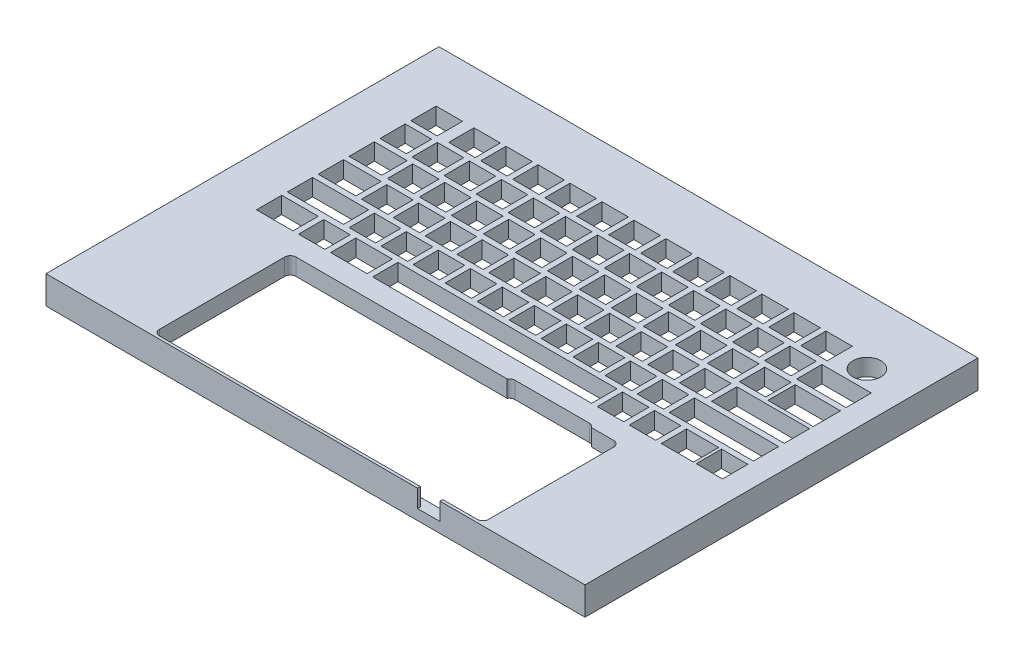
SolidWorks part; units mm, degrees
ref_plane "Front Plane" through (0, 0, 0) normal (0, 0, 1) x (1, 0, 0)
ref_plane "Top Plane" through (0, 0, 0) normal (0, 1, 0) x (1, 0, 0)
ref_plane "Right Plane" through (0, 0, 0) normal (1, 0, 0) x (0, 0, -1)
sketch "Sketch1" plane through (0, 0, 0) normal (0, 1, 0) x (1, 0, 0)
  line L0 (5.08, 5.08) -> (238.76, 5.08)
  line L1 (0, 0) -> (243.84, 0)
  line L2 (0, 0) -> (0, 177.8)
  line L3 (0, 177.8) -> (243.84, 177.8)
  line L4 (243.84, 0) -> (243.84, 177.8)
  line L5 (238.76, 5.08) -> (238.76, 172.72)
  line L6 (5.08, 172.72) -> (238.76, 172.72)
  line L7 (5.08, 5.08) -> (5.08, 172.72)
  dimension "D1" = 177.8
  dimension "D2" = 243.84
  dimension "D3" = 5.08
extrude "Boss-Extrude7" add sketch "Sketch1" along normal blind 12.7
sketch "Sketch6" plane through (0, 12.7, 0) normal (0, 1, 0) x (1, 0, 0)
  line L0 (5.08, 172.72) -> (5.08, 5.08)
  line L1 (5.08, 5.08) -> (238.76, 5.08)
  line L2 (238.76, 5.08) -> (238.76, 172.72)
  line L3 (238.76, 172.72) -> (5.08, 172.72)
extrude "Boss-Extrude8" add sketch "Sketch6" against normal blind 7.62
sketch "Sketch7" plane through (0, 12.7, 0) normal (0, 1, 0) x (1, 0, 0)
  line L0 (0, 0) -> (243.84, 0) construction
  line L1 (0, 177.8) -> (0, 0) construction
  line L2 (243.84, 0) -> (243.84, 177.8) construction
  line L3 (196.37, 1.27) -> (178.2581, 1.27)
  line L4 (47.47, 1.27) -> (47.47, 63.07)
  line L6 (196.37, 63.07) -> (196.37, 1.27)
  line L8 (47.47, 32.17) -> (0, 32.17) construction
  line L9 (196.37, 32.17) -> (243.84, 32.17) construction
  line L11 (168.0981, 0) -> (178.2581, 0)
  line L12 (178.2581, 0) -> (178.2581, 1.27)
  line L14 (157.9954, 1.27) -> (47.47, 1.27)
  line L15 (157.9954, 1.27) -> (168.0981, 1.27)
  line L16 (168.0981, 1.27) -> (168.0981, 0)
  line L18 (183.67, 64.34) -> (145.57, 64.34)
  line L20 (196.37, 63.07) -> (183.67, 63.07)
  line L21 (145.57, 63.07) -> (47.47, 63.07)
  line L22 (183.67, 63.07) -> (183.67, 64.34)
  line L23 (145.57, 63.07) -> (145.57, 64.34)
  dimension "D1" = 1.27
  dimension "D2" = 148.9
  dimension "D3" = 61.8
  dimension "D4" = 10.16
  dimension "D5" = 38.1
  dimension "D6" = 12.7
  dimension "D7" = 1.27
extrude "Cut-Extrude2" cut sketch "Sketch7" against normal blind 8 contours L4 L21 L23 L18 L22 L20 L6 L3 L12 L11 L16 L15 L14
fillet "Fillet1" radius 2.54 4 edges at (47.47, 8.89, -63.07) (47.47, 8.7, -1.27) (196.37, 8.7, -1.27) (196.37, 8.89, -63.07)
fillet "Fillet2" radius 2.54 2 edges at (145.57, 8.89, -64.34) (183.67, 8.89, -64.34)
sketch "Sketch8" plane through (0, 12.7, 0) normal (0, 1, 0) x (1, 0, 0)
  line L0 (50.5293, 86.591) -> (50.5293, 97.9956)
  line L1 (50.5293, 97.9956) -> (62.5181, 97.9956)
  line L2 (62.5181, 97.9956) -> (62.5181, 86.591)
  line L3 (62.5181, 86.591) -> (50.5293, 86.591)
  line L4 (76.9961, 86.591) -> (65.0073, 86.591)
  line L5 (65.0073, 86.591) -> (65.0073, 97.9956)
  line L6 (65.0073, 97.9956) -> (76.9961, 97.9956)
  line L7 (76.9961, 97.9956) -> (76.9961, 86.591)
  line L8 (91.4741, 86.591) -> (79.4853, 86.591)
  line L9 (79.4853, 86.591) -> (79.4853, 97.9956)
  line L10 (79.4853, 97.9956) -> (91.4741, 97.9956)
  line L11 (91.4741, 97.9956) -> (91.4741, 86.591)
  line L12 (105.9521, 86.591) -> (93.9633, 86.591)
  line L13 (93.9633, 86.591) -> (93.9633, 97.9956)
  line L14 (93.9633, 97.9956) -> (105.9521, 97.9956)
  line L15 (105.9521, 97.9956) -> (105.9521, 86.591)
  line L16 (120.4301, 86.591) -> (108.4413, 86.591)
  line L17 (108.4413, 86.591) -> (108.4413, 97.9956)
  line L18 (108.4413, 97.9956) -> (120.4301, 97.9956)
  line L19 (120.4301, 97.9956) -> (120.4301, 86.591)
  line L20 (134.9081, 86.591) -> (122.9193, 86.591)
  line L21 (122.9193, 86.591) -> (122.9193, 97.9956)
  line L22 (122.9193, 97.9956) -> (134.9081, 97.9956)
  line L23 (134.9081, 97.9956) -> (134.9081, 86.591)
  line L24 (149.3861, 86.591) -> (137.3973, 86.591)
  line L25 (137.3973, 86.591) -> (137.3973, 97.9956)
  line L26 (137.3973, 97.9956) -> (149.3861, 97.9956)
  line L27 (149.3861, 97.9956) -> (149.3861, 86.591)
  line L28 (163.8641, 86.591) -> (151.8753, 86.591)
  line L29 (151.8753, 86.591) -> (151.8753, 97.9956)
  line L30 (151.8753, 97.9956) -> (163.8641, 97.9956)
  line L31 (163.8641, 97.9956) -> (163.8641, 86.591)
  line L32 (178.3421, 86.591) -> (166.3533, 86.591)
  line L33 (166.3533, 86.591) -> (166.3533, 97.9956)
  line L34 (166.3533, 97.9956) -> (178.3421, 97.9956)
  line L35 (178.3421, 97.9956) -> (178.3421, 86.591)
  line L36 (192.8201, 86.591) -> (180.8313, 86.591)
  line L37 (180.8313, 86.591) -> (180.8313, 97.9956)
  line L38 (180.8313, 97.9956) -> (192.8201, 97.9956)
  line L39 (192.8201, 97.9956) -> (192.8201, 86.591)
  line L40 (120.4301, 92.2933) -> (122.9193, 92.2933) construction
  line L43 (120.4301, 92.2933) -> (0, 92.2933) construction
  line L44 (0, 177.8) -> (0, 0) construction
  line L45 (47.9893, 86.591) -> (22.5893, 86.591)
  line L46 (22.5893, 86.591) -> (22.5893, 97.9956)
  line L47 (22.5893, 97.9956) -> (47.9893, 97.9956)
  line L48 (47.9893, 97.9956) -> (47.9893, 86.591)
  line L55 (195.3601, 97.9956) -> (195.3601, 86.591)
  line L56 (195.3601, 86.591) -> (233.4601, 86.591)
  line L57 (233.4601, 86.591) -> (233.4601, 97.9956)
  line L58 (233.4601, 97.9956) -> (195.3601, 97.9956)
  line L59 (192.8201, 86.591) -> (195.3601, 86.591) construction
  line L60 (192.8201, 97.9956) -> (195.3601, 97.9956) construction
  line L61 (75.1673, 72.621) -> (75.1673, 84.051)
  line L62 (75.1673, 84.051) -> (174.2273, 84.051)
  line L63 (174.2273, 84.051) -> (174.2273, 72.621)
  line L64 (174.2273, 72.621) -> (75.1673, 72.621)
  line L65 (72.6273, 72.6364) -> (72.6273, 84.051)
  line L66 (72.6273, 84.051) -> (56.1173, 84.051)
  line L67 (56.1173, 84.051) -> (56.1173, 72.6364)
  line L68 (56.1173, 72.6364) -> (72.6273, 72.6364)
  line L69 (53.5773, 72.621) -> (53.5773, 84.051)
  line L70 (53.5773, 84.051) -> (41.6393, 84.051)
  line L71 (41.6393, 84.051) -> (41.6393, 72.621)
  line L72 (41.6393, 72.621) -> (53.5773, 72.621)
  line L73 (39.0993, 72.621) -> (39.0993, 84.051)
  line L74 (39.0993, 84.051) -> (22.5893, 84.051)
  line L75 (22.5893, 84.051) -> (22.5893, 72.621)
  line L76 (22.5893, 72.621) -> (39.0993, 72.621)
  line L78 (188.7052, 72.6364) -> (188.7052, 84.0664)
  line L79 (188.7052, 84.0664) -> (176.7672, 84.0664)
  line L80 (176.7672, 84.0664) -> (176.7672, 72.6364)
  line L81 (176.7672, 72.6364) -> (188.7052, 72.6364)
  line L96 (42.1943, 111.9656) -> (42.1943, 100.5356)
  line L97 (42.1943, 100.5356) -> (54.1323, 100.5356)
  line L98 (54.1323, 100.5356) -> (54.1323, 111.9656)
  line L99 (54.1323, 111.9656) -> (42.1943, 111.9656)
  line L100 (68.5217, 111.9656) -> (56.5837, 111.9656)
  line L101 (56.5837, 111.9656) -> (56.5837, 100.5356)
  line L102 (56.5837, 100.5356) -> (68.5217, 100.5356)
  line L103 (68.5217, 100.5356) -> (68.5217, 111.9656)
  line L104 (82.911, 111.9656) -> (70.973, 111.9656)
  line L105 (70.973, 111.9656) -> (70.973, 100.5356)
  line L106 (70.973, 100.5356) -> (82.911, 100.5356)
  line L107 (82.911, 100.5356) -> (82.911, 111.9656)
  line L108 (97.3003, 111.9656) -> (85.3623, 111.9656)
  line L109 (85.3623, 111.9656) -> (85.3623, 100.5356)
  line L110 (85.3623, 100.5356) -> (97.3003, 100.5356)
  line L111 (97.3003, 100.5356) -> (97.3003, 111.9656)
  line L112 (111.6896, 111.9656) -> (99.7516, 111.9656)
  line L113 (99.7516, 111.9656) -> (99.7516, 100.5356)
  line L114 (99.7516, 100.5356) -> (111.6896, 100.5356)
  line L115 (111.6896, 100.5356) -> (111.6896, 111.9656)
  line L116 (126.079, 111.9656) -> (114.141, 111.9656)
  line L117 (114.141, 111.9656) -> (114.141, 100.5356)
  line L118 (114.141, 100.5356) -> (126.079, 100.5356)
  line L119 (126.079, 100.5356) -> (126.079, 111.9656)
  line L120 (140.4683, 111.9656) -> (128.5303, 111.9656)
  line L121 (128.5303, 111.9656) -> (128.5303, 100.5356)
  line L122 (128.5303, 100.5356) -> (140.4683, 100.5356)
  line L123 (140.4683, 100.5356) -> (140.4683, 111.9656)
  line L124 (154.8576, 111.9656) -> (142.9196, 111.9656)
  line L125 (142.9196, 111.9656) -> (142.9196, 100.5356)
  line L126 (142.9196, 100.5356) -> (154.8576, 100.5356)
  line L127 (154.8576, 100.5356) -> (154.8576, 111.9656)
  line L128 (169.247, 111.9656) -> (157.309, 111.9656)
  line L129 (157.309, 111.9656) -> (157.309, 100.5356)
  line L130 (157.309, 100.5356) -> (169.247, 100.5356)
  line L131 (169.247, 100.5356) -> (169.247, 111.9656)
  line L132 (183.6363, 111.9656) -> (171.6983, 111.9656)
  line L133 (171.6983, 111.9656) -> (171.6983, 100.5356)
  line L134 (171.6983, 100.5356) -> (183.6363, 100.5356)
  line L135 (183.6363, 100.5356) -> (183.6363, 111.9656)
  line L136 (198.0256, 111.9656) -> (186.0876, 111.9656)
  line L137 (186.0876, 111.9656) -> (186.0876, 100.5356)
  line L138 (186.0876, 100.5356) -> (198.0256, 100.5356)
  line L139 (198.0256, 100.5356) -> (198.0256, 111.9656)
  line L140 (39.6543, 100.5356) -> (22.5893, 100.5356)
  line L141 (22.5893, 100.5356) -> (22.5893, 111.9656)
  line L142 (22.5893, 111.9656) -> (39.6543, 111.9656)
  line L143 (39.6543, 111.9656) -> (39.6543, 100.5356)
  line L144 (200.5656, 111.9656) -> (200.5656, 100.5356)
  line L145 (200.5656, 100.5356) -> (233.4601, 100.5356)
  line L146 (233.4601, 100.5356) -> (233.4601, 111.9656)
  line L147 (233.4601, 111.9656) -> (200.5656, 111.9656)
  line L156 (51.8757, 125.9592) -> (39.9377, 125.9592)
  line L157 (39.9377, 125.9592) -> (39.9377, 114.5056)
  line L158 (39.9377, 114.5056) -> (51.8757, 114.5056)
  line L159 (51.8757, 114.5056) -> (51.8757, 125.9592)
  line L196 (66.3537, 125.9592) -> (54.4157, 125.9592)
  line L197 (54.4157, 125.9592) -> (54.4157, 114.5056)
  line L198 (54.4157, 114.5056) -> (66.3537, 114.5056)
  line L199 (66.3537, 114.5056) -> (66.3537, 125.9592)
  line L200 (80.8317, 125.9592) -> (68.8937, 125.9592)
  line L201 (68.8937, 125.9592) -> (68.8937, 114.5056)
  line L202 (68.8937, 114.5056) -> (80.8317, 114.5056)
  line L203 (80.8317, 114.5056) -> (80.8317, 125.9592)
  line L204 (95.3097, 125.9592) -> (83.3717, 125.9592)
  line L205 (83.3717, 125.9592) -> (83.3717, 114.5056)
  line L206 (83.3717, 114.5056) -> (95.3097, 114.5056)
  line L207 (95.3097, 114.5056) -> (95.3097, 125.9592)
  line L208 (109.7877, 125.9592) -> (97.8497, 125.9592)
  line L209 (97.8497, 125.9592) -> (97.8497, 114.5056)
  line L210 (97.8497, 114.5056) -> (109.7877, 114.5056)
  line L211 (109.7877, 114.5056) -> (109.7877, 125.9592)
  line L212 (124.2657, 125.9592) -> (112.3277, 125.9592)
  line L213 (112.3277, 125.9592) -> (112.3277, 114.5056)
  line L214 (112.3277, 114.5056) -> (124.2657, 114.5056)
  line L215 (124.2657, 114.5056) -> (124.2657, 125.9592)
  line L216 (138.7437, 125.9592) -> (126.8057, 125.9592)
  line L217 (126.8057, 125.9592) -> (126.8057, 114.5056)
  line L218 (126.8057, 114.5056) -> (138.7437, 114.5056)
  line L219 (138.7437, 114.5056) -> (138.7437, 125.9592)
  line L220 (153.2217, 125.9592) -> (141.2837, 125.9592)
  line L221 (141.2837, 125.9592) -> (141.2837, 114.5056)
  line L222 (141.2837, 114.5056) -> (153.2217, 114.5056)
  line L223 (153.2217, 114.5056) -> (153.2217, 125.9592)
  line L224 (167.6997, 125.9592) -> (155.7617, 125.9592)
  line L225 (155.7617, 125.9592) -> (155.7617, 114.5056)
  line L226 (155.7617, 114.5056) -> (167.6997, 114.5056)
  line L227 (167.6997, 114.5056) -> (167.6997, 125.9592)
  line L228 (182.1777, 125.9592) -> (170.2397, 125.9592)
  line L229 (170.2397, 125.9592) -> (170.2397, 114.5056)
  line L230 (170.2397, 114.5056) -> (182.1777, 114.5056)
  line L231 (182.1777, 114.5056) -> (182.1777, 125.9592)
  line L232 (196.6557, 125.9592) -> (184.7177, 125.9592)
  line L233 (184.7177, 125.9592) -> (184.7177, 114.5056)
  line L234 (184.7177, 114.5056) -> (196.6557, 114.5056)
  line L235 (196.6557, 114.5056) -> (196.6557, 125.9592)
  line L236 (211.1337, 125.9592) -> (199.1957, 125.9592)
  line L237 (199.1957, 125.9592) -> (199.1957, 114.5056)
  line L238 (199.1957, 114.5056) -> (211.1337, 114.5056)
  line L239 (211.1337, 114.5056) -> (211.1337, 125.9592)
  line L240 (37.3977, 114.5056) -> (22.5893, 114.5056)
  line L241 (22.5893, 114.5056) -> (22.5893, 125.9592)
  line L242 (22.5893, 125.9592) -> (37.3977, 125.9592)
  line L243 (37.3977, 125.9592) -> (37.3977, 114.5056)
  line L244 (212.9454, 113.6508) -> (212.9454, 125.9592)
  line L245 (212.9454, 125.9592) -> (233.4601, 125.9592)
  line L246 (233.4601, 125.9592) -> (233.4601, 113.6508)
  line L247 (233.4601, 113.6508) -> (212.9454, 113.6508)
  line L248 (22.5893, 128.4992) -> (22.5893, 139.9292)
  line L249 (22.5893, 139.9292) -> (34.5273, 139.9292)
  line L250 (34.5273, 139.9292) -> (34.5273, 128.4992)
  line L251 (34.5273, 128.4992) -> (22.5893, 128.4992)
  line L252 (49.0288, 128.4992) -> (37.0908, 128.4992)
  line L253 (37.0908, 128.4992) -> (37.0908, 139.9292)
  line L254 (37.0908, 139.9292) -> (49.0288, 139.9292)
  line L255 (49.0288, 139.9292) -> (49.0288, 128.4992)
  line L256 (63.5303, 128.4992) -> (51.5923, 128.4992)
  line L257 (51.5923, 128.4992) -> (51.5923, 139.9292)
  line L258 (51.5923, 139.9292) -> (63.5303, 139.9292)
  line L259 (63.5303, 139.9292) -> (63.5303, 128.4992)
  line L260 (78.0318, 128.4992) -> (66.0938, 128.4992)
  line L261 (66.0938, 128.4992) -> (66.0938, 139.9292)
  line L262 (66.0938, 139.9292) -> (78.0318, 139.9292)
  line L263 (78.0318, 139.9292) -> (78.0318, 128.4992)
  line L264 (92.5334, 128.4992) -> (80.5954, 128.4992)
  line L265 (80.5954, 128.4992) -> (80.5954, 139.9292)
  line L266 (80.5954, 139.9292) -> (92.5334, 139.9292)
  line L267 (92.5334, 139.9292) -> (92.5334, 128.4992)
  line L268 (107.0349, 128.4992) -> (95.0969, 128.4992)
  line L269 (95.0969, 128.4992) -> (95.0969, 139.9292)
  line L270 (95.0969, 139.9292) -> (107.0349, 139.9292)
  line L271 (107.0349, 139.9292) -> (107.0349, 128.4992)
  line L272 (121.5364, 128.4992) -> (109.5984, 128.4992)
  line L273 (109.5984, 128.4992) -> (109.5984, 139.9292)
  line L274 (109.5984, 139.9292) -> (121.5364, 139.9292)
  line L275 (121.5364, 139.9292) -> (121.5364, 128.4992)
  line L276 (136.0379, 128.4992) -> (124.0999, 128.4992)
  line L277 (124.0999, 128.4992) -> (124.0999, 139.9292)
  line L278 (124.0999, 139.9292) -> (136.0379, 139.9292)
  line L279 (136.0379, 139.9292) -> (136.0379, 128.4992)
  line L280 (150.5395, 128.4992) -> (138.6015, 128.4992)
  line L281 (138.6015, 128.4992) -> (138.6015, 139.9292)
  line L282 (138.6015, 139.9292) -> (150.5395, 139.9292)
  line L283 (150.5395, 139.9292) -> (150.5395, 128.4992)
  line L284 (165.041, 128.4992) -> (153.103, 128.4992)
  line L285 (153.103, 128.4992) -> (153.103, 139.9292)
  line L286 (153.103, 139.9292) -> (165.041, 139.9292)
  line L287 (165.041, 139.9292) -> (165.041, 128.4992)
  line L288 (179.5425, 128.4992) -> (167.6045, 128.4992)
  line L289 (167.6045, 128.4992) -> (167.6045, 139.9292)
  line L290 (167.6045, 139.9292) -> (179.5425, 139.9292)
  line L291 (179.5425, 139.9292) -> (179.5425, 128.4992)
  line L292 (194.044, 128.4992) -> (182.106, 128.4992)
  line L293 (182.106, 128.4992) -> (182.106, 139.9292)
  line L294 (182.106, 139.9292) -> (194.044, 139.9292)
  line L295 (194.044, 139.9292) -> (194.044, 128.4992)
  line L296 (208.5455, 128.4992) -> (196.6075, 128.4992)
  line L297 (196.6075, 128.4992) -> (196.6075, 139.9292)
  line L298 (196.6075, 139.9292) -> (208.5455, 139.9292)
  line L299 (208.5455, 139.9292) -> (208.5455, 128.4992)
  line L300 (211.0855, 128.4992) -> (233.4601, 128.4992)
  line L301 (233.4601, 128.4992) -> (233.4601, 139.9292)
  line L302 (233.4601, 139.9292) -> (211.0855, 139.9292)
  line L303 (211.0855, 139.9292) -> (211.0855, 128.4992)
  line L304 (221.5221, 72.621) -> (221.5221, 84.0664)
  line L305 (221.5221, 84.0664) -> (233.4601, 84.0664)
  line L306 (233.4601, 84.0664) -> (233.4601, 72.621)
  line L307 (233.4601, 72.621) -> (221.5221, 72.621)
  line L308 (191.2452, 72.621) -> (191.2452, 84.0664)
  line L309 (191.2452, 84.0664) -> (203.1832, 84.0664)
  line L310 (203.1832, 84.0664) -> (203.1832, 72.621)
  line L311 (203.1832, 72.621) -> (191.2452, 72.621)
  line L318 (205.7232, 84.0664) -> (205.7232, 72.621)
  line L319 (205.7232, 72.621) -> (220.2767, 72.621)
  line L320 (220.2767, 72.621) -> (220.2767, 84.0664)
  line L321 (220.2767, 84.0664) -> (205.7232, 84.0664)
  line L322 (22.5893, 142.4692) -> (22.5893, 153.8992)
  line L323 (22.5893, 153.8992) -> (34.5273, 153.8992)
  line L324 (34.5273, 153.8992) -> (34.5273, 142.4692)
  line L325 (34.5273, 142.4692) -> (22.5893, 142.4692)
  line L326 (39.6543, 142.5358) -> (39.6543, 153.9658)
  line L327 (39.6543, 153.9658) -> (51.5923, 153.9658)
  line L328 (51.5923, 153.9658) -> (51.5923, 142.5358)
  line L329 (51.5923, 142.5358) -> (39.6543, 142.5358)
  line L330 (66.0703, 142.5358) -> (54.1323, 142.5358)
  line L331 (54.1323, 142.5358) -> (54.1323, 153.9658)
  line L332 (54.1323, 153.9658) -> (66.0703, 153.9658)
  line L333 (66.0703, 153.9658) -> (66.0703, 142.5358)
  line L334 (80.5483, 142.5358) -> (68.6103, 142.5358)
  line L335 (68.6103, 142.5358) -> (68.6103, 153.9658)
  line L336 (68.6103, 153.9658) -> (80.5483, 153.9658)
  line L337 (80.5483, 153.9658) -> (80.5483, 142.5358)
  line L338 (95.0263, 142.5358) -> (83.0883, 142.5358)
  line L339 (83.0883, 142.5358) -> (83.0883, 153.9658)
  line L340 (83.0883, 153.9658) -> (95.0263, 153.9658)
  line L341 (95.0263, 153.9658) -> (95.0263, 142.5358)
  line L342 (109.5043, 142.5358) -> (97.5663, 142.5358)
  line L343 (97.5663, 142.5358) -> (97.5663, 153.9658)
  line L344 (97.5663, 153.9658) -> (109.5043, 153.9658)
  line L345 (109.5043, 153.9658) -> (109.5043, 142.5358)
  line L346 (123.9823, 142.5358) -> (112.0443, 142.5358)
  line L347 (112.0443, 142.5358) -> (112.0443, 153.9658)
  line L348 (112.0443, 153.9658) -> (123.9823, 153.9658)
  line L349 (123.9823, 153.9658) -> (123.9823, 142.5358)
  line L350 (138.4603, 142.5358) -> (126.5223, 142.5358)
  line L351 (126.5223, 142.5358) -> (126.5223, 153.9658)
  line L352 (126.5223, 153.9658) -> (138.4603, 153.9658)
  line L353 (138.4603, 153.9658) -> (138.4603, 142.5358)
  line L354 (152.9383, 142.5358) -> (141.0003, 142.5358)
  line L355 (141.0003, 142.5358) -> (141.0003, 153.9658)
  line L356 (141.0003, 153.9658) -> (152.9383, 153.9658)
  line L357 (152.9383, 153.9658) -> (152.9383, 142.5358)
  line L358 (167.4163, 142.5358) -> (155.4783, 142.5358)
  line L359 (155.4783, 142.5358) -> (155.4783, 153.9658)
  line L360 (155.4783, 153.9658) -> (167.4163, 153.9658)
  line L361 (167.4163, 153.9658) -> (167.4163, 142.5358)
  line L362 (181.8943, 142.5358) -> (169.9563, 142.5358)
  line L363 (169.9563, 142.5358) -> (169.9563, 153.9658)
  line L364 (169.9563, 153.9658) -> (181.8943, 153.9658)
  line L365 (181.8943, 153.9658) -> (181.8943, 142.5358)
  line L366 (196.3723, 142.5358) -> (184.4343, 142.5358)
  line L367 (184.4343, 142.5358) -> (184.4343, 153.9658)
  line L368 (184.4343, 153.9658) -> (196.3723, 153.9658)
  line L369 (196.3723, 153.9658) -> (196.3723, 142.5358)
  line L370 (210.8503, 142.5358) -> (198.9123, 142.5358)
  line L371 (198.9123, 142.5358) -> (198.9123, 153.9658)
  line L372 (198.9123, 153.9658) -> (210.8503, 153.9658)
  line L373 (210.8503, 153.9658) -> (210.8503, 142.5358)
  line L374 (51.5923, 142.5358) -> (66.0703, 142.5358) construction
  circle A0 centre (222.9667, 148.4094) radius 6.35
  dimension "D1" = 11.9888
  dimension "D2" = 11.4046
  dimension "D4" = 25.4
  dimension "D5" = 2.4892
  dimension "D6" = 2.54
  dimension "D7" = 38.1
  dimension "D8" = 2.54
  dimension "D9" = 99.06
  dimension "D10" = 11.43
  dimension "D11" = 11.43
  dimension "D12" = 2.54
  dimension "D13" = 16.51
  dimension "D14" = 11.938
  dimension "D15" = 16.51
  dimension "D16" = 2.54
  dimension "D17" = 2.54
  dimension "D18" = 2.54
  dimension "D19" = 11.938
  dimension "D20" = 11.4454
  dimension "D21" = 11.43
  dimension "D22" = 2.54
  dimension "D23" = 11.938
  dimension "D24" = 11.938
  dimension "D25" = 2.54
  dimension "D26" = 11.43
  dimension "D27" = 1.2454
  dimension "D28" = 11.938
  dimension "D29" = 11.43
  dimension "D30" = 2.54
  dimension "D32" = 2.54
  dimension "D33" = 2.54
  dimension "D34" = 2.54
  dimension "D35" = 12
  dimension "D36" = 2.54
  dimension "D37" = 2.54
  dimension "D38" = 11.938
  dimension "D39" = 11.43
  dimension "D41" = 2.54
  dimension "D42" = 2.54
  dimension "D43" = 11.938
  dimension "D44" = 2.54
  dimension "D45" = 11.43
  dimension "D46" = 12
  dimension "D47" = 14.478
  dimension "D48" = 2.5635
  dimension "D3" = 10
  dimension "D31" = 11
  dimension "D40" = 13
extrude "Cut-Extrude3" cut sketch "Sketch8" against normal up to next (7.62 mm away) contours L302 L303 L300 L301 | L247 L246 L245 L244 | L146 L147 L144 L145 | L57 L58 L55 L56 | L307 L306 L305 L304 | L320 L321 L318 L319 | L311 L310 L309 L308 | L80 L81 L78 L79 | L39 L38 L37 L36 | L134 L135 L132 L133 | L138 L139 L136 L137 | L234 L235 L232 L233 | L238 L239 L236 L237 | L373 L372 L371 L370 | L369 L368 L367 L366 | L295 L294 L293 L292 | L365 L364 L363 L362 | L291 L290 L289 L288 | L230 L231 L228 L229 | L64 L63 L62 L61 | L75 L76 L73 L74 | L71 L72 L69 L70 | L67 L68 L65 L66 | L48 L47 L46 L45 | L143 L142 L141 L140 | L98 L99 L96 L97 | L102 L103 L100 L101 | L106 L107 L104 L105 | L110 L111 L108 L109 | L11 L10 L9 L8 | L3 L2 L1 L0 | L7 L6 L5 L4 | L114 L115 L112 L113 | L15 L14 L13 L12 | L19 L18 L17 L16 | L23 L22 L21 L20 | L118 L119 L116 L117 | L122 L123 L120 L121 | L27 L26 L25 L24 | L31 L30 L29 L28 | L126 L127 L124 L125 | L130 L131 L128 L129 | L226 L227 L224 L225 | L222 L223 L220 L221 | L218 L219 L216 L217 | L214 L215 L212 L213 | L210 L211 L208 L209 | L206 L207 L204 L205 | L202 L203 L200 L201 | L198 L199 L196 L197 | L158 L159 L156 L157 | L243 L242 L241 L240 | L251 L250 L249 L248 | L325 L324 L323 L322 | L329 L328 L327 L326 | L255 L254 L253 L252 | L259 L258 L257 L256 | L333 L332 L331 L330 | L337 L336 L335 L334 | L263 L262 L261 L260 | L267 L266 L265 L264 | L341 L340 L339 L338 | L345 L344 L343 L342 | L271 L270 L269 L268 | L275 L274 L273 L272 | L349 L348 L347 L346 | L353 L352 L351 L350 | L279 L278 L277 L276 | L283 L282 L281 L280 | L357 L356 L355 L354 | L361 L360 L359 L358 | L287 L286 L285 L284 | A0 | L34 L35 L32 L33 | L298 L299 L296 L297 region at (56.5237, 12.7, -92.2933) region at (71.0017, 12.7, -92.2933) region at (85.4797, 12.7, -92.2933) region at (99.9577, 12.7, -92.2933) region at (114.4357, 12.7, -92.2933) region at (128.9137, 12.7, -92.2933) region at (143.3917, 12.7, -92.2933) region at (157.8697, 12.7, -92.2933) region at (186.8257, 12.7, -92.2933) region at (35.2893, 12.7, -92.2933) region at (214.4101, 12.7, -92.2933) region at (124.6973, 12.7, -78.336) region at (64.3723, 12.7, -78.3437) region at (47.6083, 12.7, -78.336) region at (30.8443, 12.7, -78.336) region at (182.7362, 12.7, -78.3514) region at (48.1633, 12.7, -106.2506) region at (62.5527, 12.7, -106.2506) region at (76.942, 12.7, -106.2506) region at (91.3313, 12.7, -106.2506) region at (105.7206, 12.7, -106.2506) region at (120.11, 12.7, -106.2506) region at (134.4993, 12.7, -106.2506) region at (148.8886, 12.7, -106.2506) region at (163.278, 12.7, -106.2506) region at (177.6673, 12.7, -106.2506) region at (192.0566, 12.7, -106.2506) region at (31.1218, 12.7, -106.2506) region at (217.0128, 12.7, -106.2506) region at (45.9067, 12.7, -120.2324) region at (60.3847, 12.7, -120.2324) region at (74.8627, 12.7, -120.2324) region at (89.3407, 12.7, -120.2324) region at (103.8187, 12.7, -120.2324) region at (118.2967, 12.7, -120.2324) region at (132.7747, 12.7, -120.2324) region at (147.2527, 12.7, -120.2324) region at (161.7307, 12.7, -120.2324) region at (176.2087, 12.7, -120.2324) region at (190.6867, 12.7, -120.2324) region at (205.1647, 12.7, -120.2324) region at (29.9935, 12.7, -120.2324) region at (223.2027, 12.7, -119.805) region at (28.5583, 12.7, -134.2142) region at (43.0598, 12.7, -134.2142) region at (57.5613, 12.7, -134.2142) region at (72.0628, 12.7, -134.2142) region at (86.5644, 12.7, -134.2142) region at (101.0659, 12.7, -134.2142) region at (115.5674, 12.7, -134.2142) region at (130.0689, 12.7, -134.2142) region at (144.5705, 12.7, -134.2142) region at (159.072, 12.7, -134.2142) region at (173.5735, 12.7, -134.2142) region at (188.075, 12.7, -134.2142) region at (222.2728, 12.7, -134.2142) region at (227.4911, 12.7, -78.3437) region at (197.2142, 12.7, -78.3437) region at (213, 12.7, -78.3437) region at (28.5583, 12.7, -148.1842)
sketch "Sketch10" plane through (0, 5.08, 0) normal (0, -1, 0) x (1, 0, 0)
  line L0 (50.01, -63.07) -> (47.47, -63.07) construction
  line L1 (47.47, -63.07) -> (47.47, -60.53) construction
  arc A0 (47.47, -60.53) -> (50.01, -63.07) centre (50.01, -60.53) ccw construction
  circle A1 centre (47.47, -63.07) radius 0.7937
  dimension "D1" = 1.5875
sketch "Sketch12" plane through (0, 0, -5.08) normal (0, 0, -1) x (-1, 0, 0)
  line L0 (-47.47, 4.7) -> (-47.47, 0) construction
  line L1 (-5.08, 0) -> (-238.76, 0) construction
sketch "Sketch13" plane through (0, 0, 0) normal (0, -1, 0) x (1, 0, 0)
  line L0 (47.47, -5.08) -> (47.47, 0) construction
  line L1 (0, 0) -> (243.84, 0) construction
